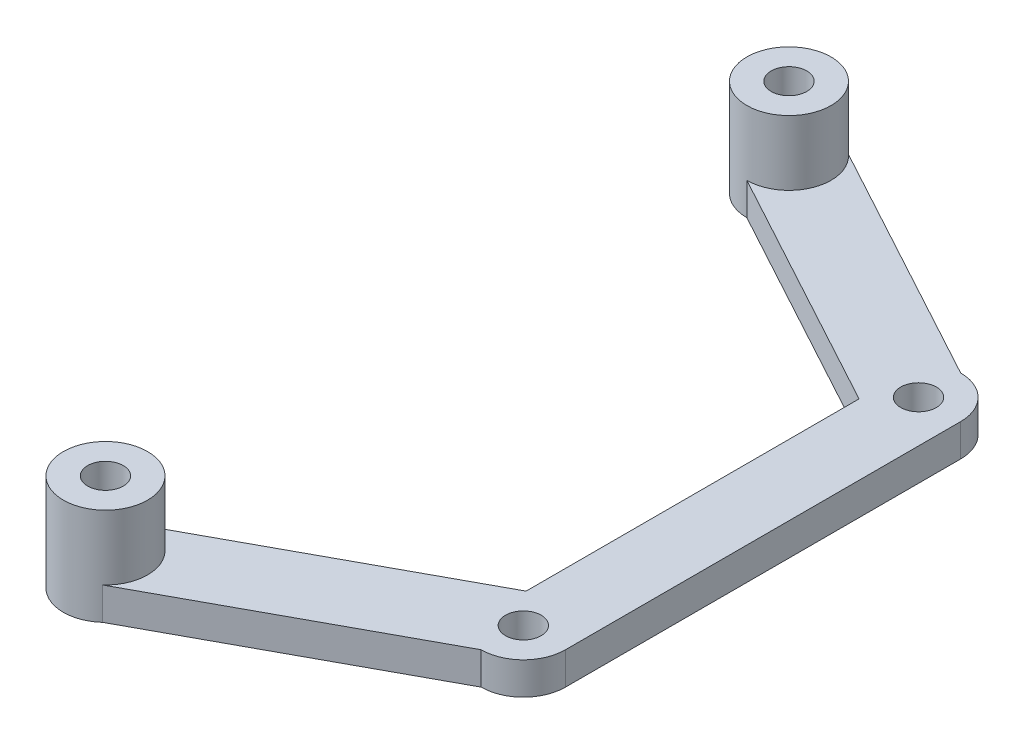
SolidWorks part; units mm, degrees
ref_plane "Front Plane" through (0, 0, 0) normal (0, 0, 1) x (1, 0, 0)
ref_plane "Top Plane" through (0, 0, 0) normal (0, 1, 0) x (1, 0, 0)
ref_plane "Right Plane" through (0, 0, 0) normal (1, 0, 0) x (0, 0, -1)
sketch "Sketch1" plane through (0, 0, 0) normal (0, 1, 0) x (1, 0, 0)
  line L1 (36.375, -26.375) -> (-36.375, -26.375) construction
  line L2 (36.375, -26.375) -> (36.375, 26.375) construction
  line L3 (36.375, 26.375) -> (-36.375, 26.375) construction
  line L4 (-36.375, -26.375) -> (-36.375, 26.375) construction
  line L5 (36.375, -26.375) -> (-36.375, 26.375) construction
  line L6 (36.375, 26.375) -> (-36.375, -26.375) construction
  circle A0 centre (-36.375, 26.375) radius 1.25
  point P0 (0, 0)
  dimension "D3" = 2.5
  dimension "D1" = 72.75
  dimension "D2" = 52.75
sketch "Sketch2" plane through (0, 0, 0) normal (0, 1, 0) x (1, 0, 0)
  line L1 (15.25, -15.25) -> (-15.25, -15.25) construction
  line L2 (15.25, -15.25) -> (15.25, 15.25) construction
  line L3 (15.25, 15.25) -> (-15.25, 15.25) construction
  line L4 (-15.25, -15.25) -> (-15.25, 15.25) construction
  line L5 (15.25, -15.25) -> (-15.25, 15.25) construction
  line L6 (15.25, 15.25) -> (-15.25, -15.25) construction
  circle A0 centre (-15.25, 15.25) radius 1.375
  point P0 (0, 0)
  dimension "D2" = 2.75
  dimension "D1" = 30.5
sketch "Sketch3" plane through (0, 0, 0) normal (0, 1, 0) x (1, 0, 0)
  line L0 (-36.375, 23.125) -> (-17.4387, 12.8475)
  line L1 (-34.1863, 28.7775) -> (-15.25, 18.5)
  line L2 (-36.375, -23.125) -> (-17.4387, -12.8475)
  line L3 (-34.1863, -28.7775) -> (-15.25, -18.5)
  line L4 (-17.4387, 12.8475) -> (-17.4387, -12.8475)
  line L5 (-12, 15.25) -> (-12, -15.25)
  arc A0 (-34.1863, 28.7775) -> (-36.375, 23.125) centre (-36.375, 26.375) ccw
  arc A1 (-12, 15.25) -> (-15.25, 18.5) centre (-15.25, 15.25) ccw
  arc A3 (-36.375, -23.125) -> (-34.1863, -28.7775) centre (-36.375, -26.375) ccw
  arc A4 (-15.25, -18.5) -> (-12, -15.25) centre (-15.25, -15.25) ccw
  circle A5 centre (-36.375, 26.375) radius 1.375
  circle A6 centre (-15.25, 15.25) radius 1.375
  circle A7 centre (-15.25, -15.25) radius 1.375
  circle A8 centre (-36.375, -26.375) radius 1.375
  dimension "D1" = 6.5
  dimension "D2" = 21.5455
  dimension "D4" = 2.75
extrude "Boss-Extrude1" add sketch "Sketch3" along normal blind 2.5
sketch "Sketch4" plane through (0, 2.5, 0) normal (0, 1, 0) x (1, 0, 0)
  circle A0 centre (-36.375, 26.375) radius 3.25
  circle A1 centre (-36.375, 26.375) radius 1.375
  circle A2 centre (-36.375, -26.375) radius 3.25
  circle A3 centre (-36.375, -26.375) radius 1.375
  dimension "D1" = 6.5
  dimension "D2" = 2.75
extrude "Boss-Extrude2" add sketch "Sketch4" along normal blind 5
